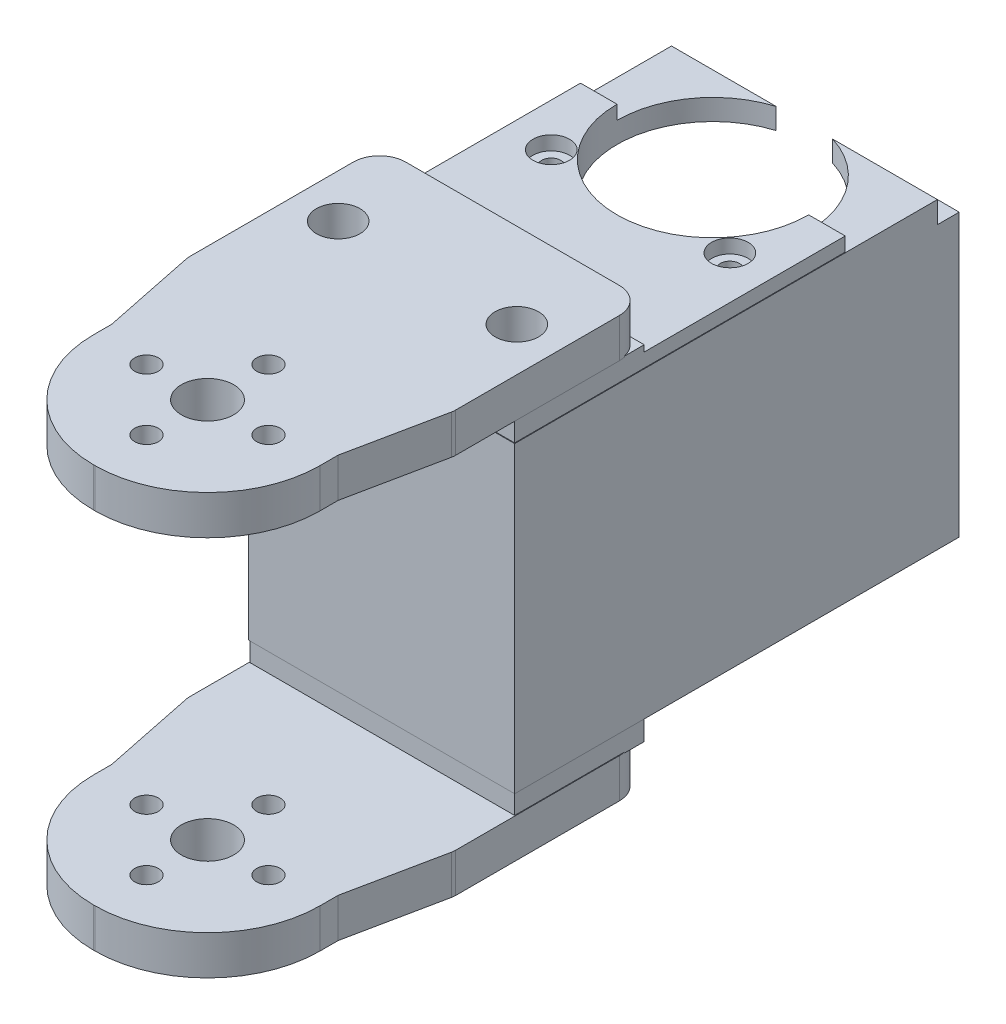
SolidWorks part; units mm, degrees
ref_plane "Front Plane" through (0, 0, 0) normal (0, 0, 1) x (1, 0, 0)
ref_plane "Top Plane" through (0, 0, 0) normal (0, 1, 0) x (1, 0, 0)
ref_plane "Right Plane" through (0, 0, 0) normal (1, 0, 0) x (0, 0, -1)
ref_plane "PY_m23_125" through (0, -23.125, 0) normal (0, 1, 0) x (1, 0, 0)
sketch "S_prism1" plane through (0, -23.125, 0) normal (0, 1, 0) x (1, 0, 0)
  line L0 (-13, 2) -> (-15.2191, 12.8008)
  line L1 (-15.26, 13.2033) -> (-15.26, 32)
  line L2 (-12.26, 35) -> (12.26, 35)
  line L3 (15.26, 32) -> (15.26, 13.2033)
  line L4 (15.2191, 12.8008) -> (13, 2)
  line L5 (13, 2) -> (13, -0.1)
  line L6 (0.1, -13) -> (-0.1, -13)
  line L7 (-13, -0.1) -> (-13, 2)
  arc A0 (-15.2191, 12.8008) -> (-15.26, 13.2033) centre (-13.2498, 13.2042) cw
  arc A1 (-15.26, 32) -> (-12.26, 35) centre (-12.2599, 31.9999) cw
  arc A2 (12.26, 35) -> (15.26, 32) centre (12.2599, 31.9999) cw
  arc A3 (15.26, 13.2033) -> (15.2191, 12.8008) centre (13.2498, 13.2042) cw
  arc A4 (13, -0.1) -> (0.1, -13) centre (0.1001, -0.1001) cw
  arc A5 (-0.1, -13) -> (-13, -0.1) centre (-0.1001, -0.1001) cw
extrude "Boss_1" add sketch "S_prism1" along normal blind 4.5
ref_plane "PY_p18_625" through (0, 18.625, 0) normal (0, 1, 0) x (1, 0, 0)
sketch "S_cyl2" plane through (0, 18.625, 0) normal (0, 1, 0) x (1, 0, 0)
  circle A0 centre (0, 0) radius 9
  dimension "D1_S_cyl2" = 18
extrude "Boss_2" add sketch "S_cyl2" along normal blind 2
ref_plane "PY_p20_625" through (0, 20.625, 0) normal (0, 1, 0) x (1, 0, 0)
sketch "S_prism3" plane through (0, 20.625, 0) normal (0, 1, 0) x (1, 0, 0)
  line L0 (-13, 2) -> (-15.2191, 12.8008)
  line L1 (-15.26, 13.2033) -> (-15.26, 32)
  line L2 (-12.26, 35) -> (12.26, 35)
  line L3 (15.26, 32) -> (15.26, 13.2033)
  line L4 (15.2191, 12.8008) -> (13, 2)
  line L5 (13, 2) -> (13, -0.1)
  line L6 (0.1, -13) -> (-0.1, -13)
  line L7 (-13, -0.1) -> (-13, 2)
  arc A0 (-15.2191, 12.8008) -> (-15.26, 13.2033) centre (-13.2498, 13.2042) cw
  arc A1 (-15.26, 32) -> (-12.26, 35) centre (-12.2599, 31.9999) cw
  arc A2 (12.26, 35) -> (15.26, 32) centre (12.2599, 31.9999) cw
  arc A3 (15.26, 13.2033) -> (15.2191, 12.8008) centre (13.2498, 13.2042) cw
  arc A4 (13, -0.1) -> (0.1, -13) centre (0.1001, -0.1001) cw
  arc A5 (-0.1, -13) -> (-13, -0.1) centre (-0.1001, -0.1001) cw
extrude "Boss_3" add sketch "S_prism3" along normal blind 4.5
ref_plane "PZ_m22_490" through (0, 0, -22.49) normal (0, 0, 1) x (1, 0, 0)
sketch "S_box4" plane through (0, 0, -22.49) normal (0, 0, 1) x (1, 0, 0)
  line L0 (-15.26, -16.4) -> (15.26, -16.4)
  line L1 (15.26, -16.4) -> (15.26, 18.4)
  line L2 (15.26, 18.4) -> (-15.26, 18.4)
  line L3 (-15.26, 18.4) -> (-15.26, -16.4)
  dimension "P1" = 15.26
  dimension "P2" = 16.4
  dimension "P3" = 15.26
  dimension "P4" = 16.4
  dimension "P5" = 15.26
  dimension "P6" = 18.4
  dimension "P7" = 15.26
  dimension "P8" = 18.4
extrude "Boss_4" add sketch "S_box4" along normal blind 2.5
ref_plane "PZ_m71_010" through (0, 0, -71.01) normal (0, 0, 1) x (1, 0, 0)
sketch "S_box5" plane through (0, 0, -71.01) normal (0, 0, 1) x (1, 0, 0)
  line L0 (12.76, -16.4) -> (15.26, -16.4)
  line L1 (15.26, -16.4) -> (15.26, 18.4)
  line L2 (15.26, 18.4) -> (12.76, 18.4)
  line L3 (12.76, 18.4) -> (12.76, -16.4)
  dimension "P1" = 12.76
  dimension "P2" = 16.4
  dimension "P3" = 15.26
  dimension "P4" = 16.4
  dimension "P5" = 15.26
  dimension "P6" = 18.4
  dimension "P7" = 12.76
  dimension "P8" = 18.4
extrude "Boss_5" add sketch "S_box5" along normal blind 51.02
sketch "S_box6" plane through (0, 0, -71.01) normal (0, 0, 1) x (1, 0, 0)
  line L0 (-15.26, 16) -> (15.26, 16)
  line L1 (15.26, 16) -> (15.26, 18.4)
  line L2 (15.26, 18.4) -> (-15.26, 18.4)
  line L3 (-15.26, 18.4) -> (-15.26, 16)
  dimension "P1" = 15.26
  dimension "P2" = 16
  dimension "P3" = 15.26
  dimension "P4" = 16
  dimension "P5" = 15.26
  dimension "P6" = 18.4
  dimension "P7" = 15.26
  dimension "P8" = 18.4
extrude "Boss_6" add sketch "S_box6" along normal blind 51.02
ref_plane "PZ_m38_000" through (0, 0, -38) normal (0, 0, 1) x (1, 0, 0)
sketch "S_box7" plane through (0, 0, -38) normal (0, 0, 1) x (1, 0, 0)
  line L0 (-15.26, -16.4) -> (-12.76, -16.4)
  line L1 (-12.76, -16.4) -> (-12.76, 18.4)
  line L2 (-12.76, 18.4) -> (-15.26, 18.4)
  line L3 (-15.26, 18.4) -> (-15.26, -16.4)
  dimension "P1" = 15.26
  dimension "P2" = 16.4
  dimension "P3" = 12.76
  dimension "P4" = 16.4
  dimension "P5" = 12.76
  dimension "P6" = 18.4
  dimension "P7" = 15.26
  dimension "P8" = 18.4
extrude "Boss_7" add sketch "S_box7" along normal blind 18.01
ref_plane "PZ_m34_930" through (0, 0, -34.93) normal (0, 0, 1) x (1, 0, 0)
sketch "S_box8" plane through (0, 0, -34.93) normal (0, 0, 1) x (1, 0, 0)
  line L0 (-15.19, -18.725) -> (15.19, -18.725)
  line L1 (15.19, -18.725) -> (15.19, -16.05)
  line L2 (15.19, -16.05) -> (-15.19, -16.05)
  line L3 (-15.19, -16.05) -> (-15.19, -18.725)
  dimension "P1" = 15.19
  dimension "P2" = 18.725
  dimension "P3" = 15.19
  dimension "P4" = 18.725
  dimension "P5" = 15.19
  dimension "P6" = 16.05
  dimension "P7" = 15.19
  dimension "P8" = 16.05
extrude "Boss_8" add sketch "S_box8" along normal blind 14.87
sketch "S_box9" plane through (0, 0, -34.93) normal (0, 0, 1) x (1, 0, 0)
  line L0 (-15.19, 18.3) -> (15.19, 18.3)
  line L1 (15.19, 18.3) -> (15.19, 20.725)
  line L2 (15.19, 20.725) -> (-15.19, 20.725)
  line L3 (-15.19, 20.725) -> (-15.19, 18.3)
  dimension "P1" = 15.19
  dimension "P2" = 18.3
  dimension "P3" = 15.19
  dimension "P4" = 18.3
  dimension "P5" = 15.19
  dimension "P6" = 20.725
  dimension "P7" = 15.19
  dimension "P8" = 20.725
extrude "Boss_9" add sketch "S_box9" along normal blind 14.87
ref_plane "PZ_m58_000" through (0, 0, -58) normal (0, 0, 1) x (1, 0, 0)
sketch "S_box10" plane through (0, 0, -58) normal (0, 0, 1) x (1, 0, 0)
  line L0 (-15.19, 18.35) -> (15.19, 18.35)
  line L1 (15.19, 18.35) -> (15.19, 20)
  line L2 (15.19, 20) -> (-15.19, 20)
  line L3 (-15.19, 20) -> (-15.19, 18.35)
  dimension "P1" = 15.19
  dimension "P2" = 18.35
  dimension "P3" = 15.19
  dimension "P4" = 18.35
  dimension "P5" = 15.19
  dimension "P6" = 20
  dimension "P7" = 15.19
  dimension "P8" = 20
extrude "Boss_10" add sketch "S_box10" along normal blind 37.94
ref_plane "PY_m23_225" through (0, -23.225, 0) normal (0, 1, 0) x (1, 0, 0)
sketch "S_hole11" plane through (0, -23.225, 0) normal (0, 1, 0) x (1, 0, 0)
  circle A0 centre (0, 0) radius 3
  dimension "D1_S_hole11" = 6
extrude "Hole_11" cut sketch "S_hole11" along normal blind 4.7
sketch "S_hole12" plane through (0, -23.225, 0) normal (0, 1, 0) x (1, 0, 0)
  circle A0 centre (7, 0) radius 1.35
  dimension "D1_S_hole12" = 2.7
  dimension "P2" = 7
extrude "Hole_12" cut sketch "S_hole12" along normal blind 4.7
sketch "S_hole13" plane through (0, -23.225, 0) normal (0, 1, 0) x (1, 0, 0)
  circle A0 centre (0, -7) radius 1.35
  dimension "D1_S_hole13" = 2.7
  dimension "P2" = 7
extrude "Hole_13" cut sketch "S_hole13" along normal blind 4.7
sketch "S_hole14" plane through (0, -23.225, 0) normal (0, 1, 0) x (1, 0, 0)
  circle A0 centre (-7, 0) radius 1.35
  dimension "D1_S_hole14" = 2.7
  dimension "P2" = 7
extrude "Hole_14" cut sketch "S_hole14" along normal blind 4.7
sketch "S_hole15" plane through (0, -23.225, 0) normal (0, 1, 0) x (1, 0, 0)
  circle A0 centre (0, 7) radius 1.35
  dimension "D1_S_hole15" = 2.7
  dimension "P2" = 7
extrude "Hole_15" cut sketch "S_hole15" along normal blind 4.7
ref_plane "PY_p18_525" through (0, 18.525, 0) normal (0, 1, 0) x (1, 0, 0)
sketch "S_hole16" plane through (0, 18.525, 0) normal (0, 1, 0) x (1, 0, 0)
  circle A0 centre (0, 0) radius 3
  dimension "D1_S_hole16" = 6
extrude "Hole_16" cut sketch "S_hole16" along normal blind 6.7
sketch "S_hole17" plane through (0, 18.525, 0) normal (0, 1, 0) x (1, 0, 0)
  circle A0 centre (7, 0) radius 1.35
  dimension "D1_S_hole17" = 2.7
  dimension "P2" = 7
extrude "Hole_17" cut sketch "S_hole17" along normal blind 6.7
sketch "S_hole18" plane through (0, 18.525, 0) normal (0, 1, 0) x (1, 0, 0)
  circle A0 centre (0, -7) radius 1.35
  dimension "D1_S_hole18" = 2.7
  dimension "P2" = 7
extrude "Hole_18" cut sketch "S_hole18" along normal blind 6.7
sketch "S_hole19" plane through (0, 18.525, 0) normal (0, 1, 0) x (1, 0, 0)
  circle A0 centre (-7, 0) radius 1.35
  dimension "D1_S_hole19" = 2.7
  dimension "P2" = 7
extrude "Hole_19" cut sketch "S_hole19" along normal blind 6.7
sketch "S_hole20" plane through (0, 18.525, 0) normal (0, 1, 0) x (1, 0, 0)
  circle A0 centre (0, 7) radius 1.35
  dimension "D1_S_hole20" = 2.7
  dimension "P2" = 7
extrude "Hole_20" cut sketch "S_hole20" along normal blind 6.7
ref_plane "PY_p15_900" through (0, 15.9, 0) normal (0, 1, 0) x (1, 0, 0)
sketch "S_hole21" plane through (0, 15.9, 0) normal (0, 1, 0) x (1, 0, 0)
  circle A0 centre (0, 58) radius 11
  dimension "D1_S_hole21" = 22
  dimension "P2" = 58
extrude "Hole_21" cut sketch "S_hole21" along normal blind 2.6
sketch "S_hole22" plane through (0, 15.9, 0) normal (0, 1, 0) x (1, 0, 0)
  circle A0 centre (-10.25, 49.7) radius 1.1
  dimension "D1_S_hole22" = 2.2
  dimension "P2" = 10.25
  dimension "P3" = 49.7
extrude "Hole_22" cut sketch "S_hole22" along normal blind 2.6
sketch "S_hole23" plane through (0, 15.9, 0) normal (0, 1, 0) x (1, 0, 0)
  circle A0 centre (10.25, 49.7) radius 1.1
  dimension "D1_S_hole23" = 2.2
  dimension "P2" = 10.25
  dimension "P3" = 49.7
extrude "Hole_23" cut sketch "S_hole23" along normal blind 2.6
sketch "S_hole24" plane through (0, 15.9, 0) normal (0, 1, 0) x (1, 0, 0)
  circle A0 centre (-10.25, 25.25) radius 1.1
  dimension "D1_S_hole24" = 2.2
  dimension "P2" = 10.25
  dimension "P3" = 25.25
extrude "Hole_24" cut sketch "S_hole24" along normal blind 2.6
sketch "S_hole25" plane through (0, 15.9, 0) normal (0, 1, 0) x (1, 0, 0)
  circle A0 centre (10.25, 25.25) radius 1.1
  dimension "D1_S_hole25" = 2.2
  dimension "P2" = 10.25
  dimension "P3" = 25.25
extrude "Hole_25" cut sketch "S_hole25" along normal blind 2.6
ref_plane "PZ_m71_110" through (0, 0, -71.11) normal (0, 0, 1) x (1, 0, 0)
sketch "S_cut26" plane through (0, 0, -71.11) normal (0, 0, 1) x (1, 0, 0)
  line L0 (-15.36, 15.9) -> (15.36, 15.9)
  line L1 (15.36, 15.9) -> (15.36, 18.5)
  line L2 (15.36, 18.5) -> (-15.36, 18.5)
  line L3 (-15.36, 18.5) -> (-15.36, 15.9)
  dimension "P1" = 15.36
  dimension "P2" = 15.9
  dimension "P3" = 15.36
  dimension "P4" = 15.9
  dimension "P5" = 15.36
  dimension "P6" = 18.5
  dimension "P7" = 15.36
  dimension "P8" = 18.5
extrude "Pocket_26" cut sketch "S_cut26" along normal blind 2.6
ref_plane "PY_p20_050" through (0, 20.05, 0) normal (0, 1, 0) x (1, 0, 0)
sketch "S_hole27" plane through (0, 20.05, 0) normal (0, 1, 0) x (1, 0, 0)
  circle A0 centre (-10.25, 25.25) radius 2.5
  dimension "D1_S_hole27" = 5
  dimension "P2" = 10.25
  dimension "P3" = 25.25
extrude "Hole_27" cut sketch "S_hole27" along normal blind 5.175
sketch "S_hole28" plane through (0, 20.05, 0) normal (0, 1, 0) x (1, 0, 0)
  circle A0 centre (10.25, 25.25) radius 2.5
  dimension "D1_S_hole28" = 5
  dimension "P2" = 10.25
  dimension "P3" = 25.25
extrude "Hole_28" cut sketch "S_hole28" along normal blind 5.175
ref_plane "PY_p18_300" through (0, 18.3, 0) normal (0, 1, 0) x (1, 0, 0)
sketch "S_hole29" plane through (0, 18.3, 0) normal (0, 1, 0) x (1, 0, 0)
  circle A0 centre (0, 58) radius 11
  dimension "D1_S_hole29" = 22
  dimension "P2" = 58
extrude "Hole_29" cut sketch "S_hole29" along normal blind 1.8
sketch "S_hole30" plane through (0, 18.3, 0) normal (0, 1, 0) x (1, 0, 0)
  circle A0 centre (-10.25, 49.7) radius 1.1
  dimension "D1_S_hole30" = 2.2
  dimension "P2" = 10.25
  dimension "P3" = 49.7
extrude "Hole_30" cut sketch "S_hole30" along normal blind 1.8
ref_plane "PY_p18_400" through (0, 18.4, 0) normal (0, 1, 0) x (1, 0, 0)
sketch "S_hole31" plane through (0, 18.4, 0) normal (0, 1, 0) x (1, 0, 0)
  circle A0 centre (-10.25, 49.7) radius 2.1
  dimension "D1_S_hole31" = 4.2
  dimension "P2" = 10.25
  dimension "P3" = 49.7
extrude "Hole_31" cut sketch "S_hole31" along normal blind 1.7
sketch "S_hole32" plane through (0, 18.3, 0) normal (0, 1, 0) x (1, 0, 0)
  circle A0 centre (10.25, 49.7) radius 1.1
  dimension "D1_S_hole32" = 2.2
  dimension "P2" = 10.25
  dimension "P3" = 49.7
extrude "Hole_32" cut sketch "S_hole32" along normal blind 1.8
sketch "S_hole33" plane through (0, 18.4, 0) normal (0, 1, 0) x (1, 0, 0)
  circle A0 centre (10.25, 49.7) radius 2.1
  dimension "D1_S_hole33" = 4.2
  dimension "P2" = 10.25
  dimension "P3" = 49.7
extrude "Hole_33" cut sketch "S_hole33" along normal blind 1.7
sketch "S_hole34" plane through (0, 18.3, 0) normal (0, 1, 0) x (1, 0, 0)
  circle A0 centre (-10.25, 25.25) radius 1.1
  dimension "D1_S_hole34" = 2.2
  dimension "P2" = 10.25
  dimension "P3" = 25.25
extrude "Hole_34" cut sketch "S_hole34" along normal blind 1.8
sketch "S_hole35" plane through (0, 18.4, 0) normal (0, 1, 0) x (1, 0, 0)
  circle A0 centre (-10.25, 25.25) radius 2.1
  dimension "D1_S_hole35" = 4.2
  dimension "P2" = 10.25
  dimension "P3" = 25.25
extrude "Hole_35" cut sketch "S_hole35" along normal blind 1.7
sketch "S_hole36" plane through (0, 18.3, 0) normal (0, 1, 0) x (1, 0, 0)
  circle A0 centre (10.25, 25.25) radius 1.1
  dimension "D1_S_hole36" = 2.2
  dimension "P2" = 10.25
  dimension "P3" = 25.25
extrude "Hole_36" cut sketch "S_hole36" along normal blind 1.8
sketch "S_hole37" plane through (0, 18.4, 0) normal (0, 1, 0) x (1, 0, 0)
  circle A0 centre (10.25, 25.25) radius 2.1
  dimension "D1_S_hole37" = 4.2
  dimension "P2" = 10.25
  dimension "P3" = 25.25
extrude "Hole_37" cut sketch "S_hole37" along normal blind 1.7
equation "\"plate_t\" = 3"
equation "\"clearance\" = 0.4"
